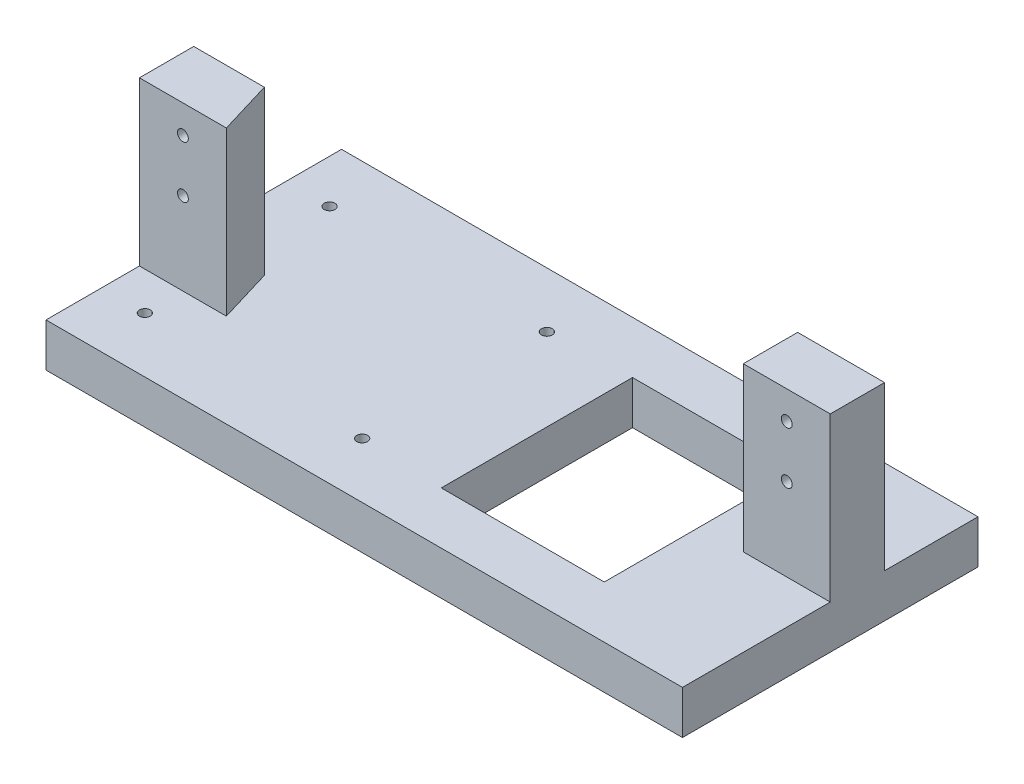
SolidWorks part; units mm, degrees
ref_plane "Front Plane" through (0, 0, 0) normal (0, 0, 1) x (1, 0, 0)
ref_plane "Top Plane" through (0, 0, 0) normal (0, 1, 0) x (1, 0, 0)
ref_plane "Right Plane" through (0, 0, 0) normal (1, 0, 0) x (0, 0, -1)
sketch "Sketch1" plane through (0, 0, 0) normal (0, 1, 0) x (1, 0, 0)
  line L1 (0, 0) -> (74.3991, 0)
  line L2 (0, 0) -> (0, 34.544)
  line L3 (0, 34.544) -> (74.3991, 34.544)
  line L4 (74.3991, 0) -> (74.3991, 34.544)
  dimension "D1" = 34.544
  dimension "D2" = 74.3991
extrude "Boss-Extrude1" add sketch "Sketch1" along normal blind 5.08
sketch "Sketch2" plane through (0, 5.08, 0) normal (0, 1, 0) x (1, 0, 0)
  line L0 (0, 17.272) -> (74.3991, 17.272) construction
  line L1 (0, 34.544) -> (0, 0) construction
  line L2 (74.3991, 0) -> (74.3991, 34.544) construction
  line L3 (10.16, 23.622) -> (64.2391, 23.622) construction
  line L4 (0, 23.622) -> (10.16, 23.622) construction
  line L5 (0, 23.622) -> (0, 17.272) construction
  line L6 (0, 17.272) -> (10.16, 17.272) construction
  line L7 (10.16, 23.622) -> (10.16, 17.272) construction
  line L8 (74.3991, 23.622) -> (64.2391, 23.622)
  line L9 (74.3991, 23.622) -> (74.3991, 17.272)
  line L10 (74.3991, 17.272) -> (64.2391, 17.272)
  line L11 (64.2391, 23.622) -> (64.2391, 17.272)
  line L12 (74.3991, 34.544) -> (0, 34.544) construction
  line L14 (0, 17.272) -> (10.16, 17.272)
  line L15 (0, 17.272) -> (0, 10.922)
  line L16 (0, 10.922) -> (10.16, 10.922)
  line L17 (10.16, 17.272) -> (10.16, 10.922)
  dimension "D1" = 10.16
  dimension "D2" = 6.35
  dimension "D3" = 6.35
  dimension "D4" = 10.16
  dimension "D5" = 10.922
  dimension "D6" = 6.35
  dimension "D7" = 10.16
extrude "Boss-Extrude2" add sketch "Sketch2" along normal blind 19.05
sketch "Sketch3" plane through (0, 0, -23.622) normal (0, 0, -1) x (-1, 0, 0)
  line L0 (-69.3191, 24.13) -> (-69.3191, 20.828) construction
  line L1 (-74.3991, 24.13) -> (-64.2391, 24.13) construction
  line L2 (-69.3191, 20.828) -> (-69.3191, 14.732) construction
  circle A0 centre (-69.3191, 20.828) radius 0.635
  circle A1 centre (-69.3191, 14.732) radius 0.635
  dimension "D1" = 1.27
  dimension "D2" = 1.27
  dimension "D3" = 3.302
  dimension "D4" = 6.096
extrude "Cut-Extrude1" cut sketch "Sketch3" against normal through all
sketch "Sketch4" plane through (0, 5.08, 0) normal (0, 1, 0) x (1, 0, 0)
  line L0 (74.3991, 34.544) -> (0, 34.544) construction
  line L1 (40.1091, 28.448) -> (59.1591, 28.448)
  line L2 (40.1091, 28.448) -> (40.1091, 6.096)
  line L3 (40.1091, 6.096) -> (59.1591, 6.096)
  line L4 (59.1591, 28.448) -> (59.1591, 6.096)
  line L5 (0, 0) -> (74.3991, 0) construction
  line L6 (64.2391, 23.622) -> (64.2391, 17.272) construction
  dimension "D1" = 6.096
  dimension "D2" = 6.096
  dimension "D3" = 19.05
  dimension "D4" = 5.08
extrude "Cut-Extrude2" cut sketch "Sketch4" against normal through all
sketch "Sketch5" plane through (0, 0, 0) normal (0, -1, 0) x (-1, 0, 0)
  line L0 (-5.08, 17.272) -> (-74.3991, 17.272) construction
  line L1 (-5.08, 6.477) -> (-30.48, 6.477) construction
  line L2 (-5.08, 6.477) -> (-5.08, 28.067) construction
  line L3 (-5.08, 28.067) -> (-30.48, 28.067) construction
  line L4 (-30.48, 6.477) -> (-30.48, 28.067) construction
  line L5 (0, 34.544) -> (0, 17.272) construction
  line L6 (-74.3991, 0) -> (-74.3991, 34.544) construction
  circle A0 centre (-5.08, 28.067) radius 0.635
  circle A1 centre (-30.48, 28.067) radius 0.635
  circle A2 centre (-30.48, 6.477) radius 0.635
  circle A3 centre (-5.08, 6.477) radius 0.635
  point P8 (-5.08, 17.272)
  dimension "D4" = 1.27
  dimension "D1" = 25.4
  dimension "D2" = 21.59
  dimension "D3" = 5.08
extrude "Cut-Extrude3" cut sketch "Sketch5" against normal through all
sketch "Sketch6" plane through (0, 0, -17.272) normal (0, 0, -1) x (-1, 0, 0)
  line L0 (-5.08, 24.13) -> (-5.08, 5.08) construction
  line L1 (-10.16, 24.13) -> (0, 24.13) construction
  line L2 (-10.16, 5.08) -> (0, 5.08) construction
  line L3 (-69.3191, 20.828) -> (-5.08, 20.828) construction
  line L4 (-69.3191, 14.732) -> (-5.08, 14.732) construction
  circle A0 centre (-69.3191, 20.828) radius 0.635 construction
  circle A1 centre (-69.3191, 14.732) radius 0.635 construction
  circle A2 centre (-69.3191, 20.828) radius 0.635 construction
  circle A3 centre (-69.3191, 14.732) radius 0.635 construction
  circle A4 centre (-5.08, 20.828) radius 0.635
  circle A5 centre (-5.08, 14.732) radius 0.635
extrude "Cut-Extrude4" cut sketch "Sketch6" against normal through all
sketch "Sketch8" plane through (0, 24.13, 0) normal (0, 1, 0) x (1, 0, 0)
  line L0 (10.16, 10.922) -> (8.255, 17.272)
  line L1 (10.16, 17.272) -> (0, 17.272) construction
  line L2 (8.255, 17.272) -> (10.16, 17.272)
  line L3 (10.16, 17.272) -> (10.16, 10.922)
  dimension "D1" = 1.905
extrude "Cut-Extrude5" cut sketch "Sketch8" against normal up to surface (19.05 mm away) up to face at (5.08, 5.08, -7.112)
